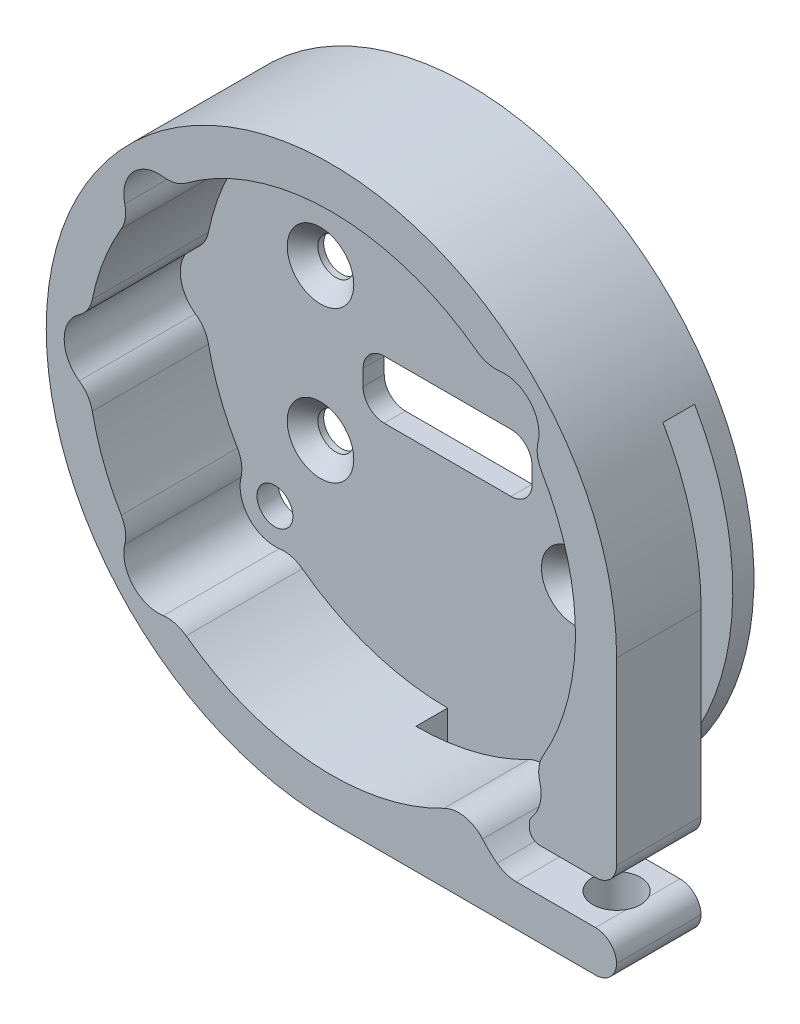
SolidWorks part; units mm, degrees
material "Сплав 2024"
ref_plane "Спереди" through (0, 0, 0) normal (0, 0, 1) x (1, 0, 0)
ref_plane "Сверху" through (0, 0, 0) normal (0, 1, 0) x (1, 0, 0)
ref_plane "Справа" through (0, 0, 0) normal (1, 0, 0) x (0, 0, -1)
sketch "Эскиз1" plane through (0, 0, 0) normal (0, 0, 1) x (1, 0, 0)
  circle A0 centre (0, 0) radius 23.1
  circle A1 centre (0, 0) radius 27
  dimension "D1" = 54
  dimension "D2" = 46.2
extrude "Бобышка-Вытянуть1" add sketch "Эскиз1" along normal blind 11
sketch "Эскиз2" plane through (0, 0, 0) normal (0, 0, -1) x (-1, 0, 0)
  circle A0 centre (0, 0) radius 27 construction
  circle A1 centre (0, 0) radius 27
extrude "Бобышка-Вытянуть2" add sketch "Эскиз2" along normal blind 2
sketch "Эскиз3" plane through (0, 0, 11) normal (0, 0, 1) x (1, 0, 0)
  line L0 (0, -27) -> (27, -27)
  line L1 (27, -27) -> (27, 0)
  circle A0 centre (0, 0) radius 27 construction
  arc A1 (27, 0) -> (0, -27) centre (0, 0) cw
extrude "Бобышка-Вытянуть3" add sketch "Эскиз3" against normal blind 8
sketch "Эскиз4" plane through (0, 0, 11) normal (0, 0, 1) x (1, 0, 0)
  line L0 (0, -23.1) -> (27, -23.1)
  line L1 (27, -27) -> (27, 0) construction
  line L2 (27, -23.1) -> (27, -19)
  line L3 (27, -19) -> (13.1381, -19)
  circle A0 centre (0, 0) radius 23.1 construction
  circle A1 centre (0, 0) radius 23.1 construction
  arc A2 (0, -23.1) -> (13.1381, -19) centre (0, 0) ccw
  dimension "D1" = 4.1
extrude "Вырез-Вытянуть1" cut sketch "Эскиз4" against normal blind 8
sketch "Эскиз5" plane through (0, -27, 0) normal (0, -1, 0) x (1, 0, 0)
  line L0 (23, 11) -> (23, 3) construction
  line L1 (0, 11) -> (27, 11) construction
  line L2 (0, 3) -> (27, 3) construction
  line L3 (27, 3) -> (27, 11) construction
  point P8 (23, 7)
  dimension "D1" = 4
hole_wizard "Отверстие с зазором M41" positions "Эскиз7" profile "Эскиз6" hole size "M4" standard "Ansi Metric" end condition up to next
sketch "Эскиз7" plane through (0, -27, 0) normal (0, -1, 0) x (-1, 0, 0)
  point P0 (-23, -7)
sketch "Эскиз6" plane through (23, -27, 7) normal (1, 0, 0) x (0, 0, -1)
  line L0 (0, 0) -> (0, 3.9)
  line L1 (0, 3.9) -> (2.25, 3.9)
  line L2 (2.25, 3.9) -> (2.25, 0)
  line L5 (2.25, 0) -> (0, 0)
  line L11 (0, -6.35) -> (0, 107.95) construction
  dimension "Диаметр сквозного отверстия" = 4.5
  dimension "Глубина сквозного отверстия" = 3.9
hole_wizard "Отверстие обработанное метчиком M4x0.71" positions "Эскиз9" profile "Эскиз8" tap size "M4x0.7" standard "Ansi Metric"
sketch "Эскиз9" plane through (0, -19, 0) normal (0, -1, 0) x (-1, 0, 0)
  point P0 (-23, -7)
cosmetic thread "Отверстие резьбы1" parameters "D1"=7, "D2"=4
sketch "Эскиз8" plane through (23, -19, 7) normal (1, 0, 0) x (0, 0, -1)
  line L0 (0, 0) -> (0, 11.4914)
  line L1 (0, 11.4914) -> (1.65, 10.5)
  line L2 (1.65, 10.5) -> (1.65, 0)
  line L5 (1.65, 0) -> (0, 0)
  line L10 (0, 11.4914) -> (-1.65, 10.5) construction
  line L11 (0, -6.35) -> (0, 107.95) construction
  dimension "Диаметр сверла" = 3.3
  dimension "Глубина сверла" = 10.5
  dimension "Угол заточки сверла" = 118
sketch "Эскиз10" plane through (0, 0, 3) normal (0, 0, 1) x (1, 0, 0)
  line L0 (0, 0) -> (0, -29.8506) construction
  line L1 (0, 0) -> (26.6177, 15.3678) construction
  line L2 (20.0052, 11.55) -> (23.3827, 13.5)
  line L3 (0, -23.1) -> (0, -27)
  circle A0 centre (0, 0) radius 23.1 construction
  arc A1 (27, 0) -> (0, -27) centre (0, 0) ccw construction
  arc A2 (0, -23.1) -> (20.0052, 11.55) centre (0, 0) ccw
  arc A3 (0, -27) -> (23.3827, 13.5) centre (0, 0) ccw
  point P3 (0, -23.1)
  point P5 (0, -27)
  point P8 (20.0052, 11.55)
  point P10 (23.3827, 13.5)
  dimension "D1" = 120
extrude "Вырез-Вытянуть2" cut sketch "Эскиз10" against normal blind 3
fillet "Скругление1" radius 2 3 edges at (27, -23.1, 7) (27, -27, 7) (27, -19, 7)
sketch "Эскиз11" plane through (0, 0, 0) normal (0, 0, 1) x (1, 0, 0)
  line L1 (-8, 2.75) -> (8, 2.75)
  line L2 (-8, 2.75) -> (-8, -2.75)
  line L3 (-8, -2.75) -> (8, -2.75)
  line L4 (8, 2.75) -> (8, -2.75)
  line L5 (-8, 2.75) -> (8, -2.75) construction
  line L6 (-8, -2.75) -> (8, 2.75) construction
  point P0 (0, 0)
  dimension "D2" = 5.5
  dimension "D1" = 16
extrude "Вырез-Вытянуть3" cut sketch "Эскиз11" against normal through all
sketch "Эскиз12" plane through (0, 0, 11) normal (0, 0, 1) x (1, 0, 0)
  circle A0 centre (0, 22) radius 3
  circle A1 centre (-22, 0) radius 3
  point P7 (0, 0)
  dimension "D1" = 6
  dimension "D2" = 22
  dimension "D3" = 2
extrude "Вырез-Вытянуть4" [suppressed] cut sketch "Эскиз12" against normal up to surface (11 mm away)
fillet "Скругление2" [suppressed] radius 3
sketch "Эскиз13" plane through (0, 0, -2) normal (0, 0, -1) x (-1, 0, 0)
  point P0 (0, 0)
sketch "Эскиз14" plane through (0, 0, 0) normal (0, 0, 1) x (1, 0, 0)
  line L0 (-36.5668, 0) -> (36.5668, 0) construction
  line L1 (22.6491, 20.3933) -> (-22.6491, -20.3933) construction
  line L2 (-23.4959, 21.1558) -> (23.4959, -21.1558) construction
  circle A0 centre (0, 0) radius 20.5 construction
  dimension "D1" = 41
  dimension "D2" = 42
  dimension "D3" = 96
sketch "Эскиз15" plane through (0, 0, 0) normal (0, 0, 1) x (1, 0, 0)
  line L0 (-23.4959, 21.1558) -> (23.4959, -21.1558) construction
  line L6 (-36.5668, 0) -> (36.5668, 0) construction
  line L7 (22.6491, 20.3933) -> (-22.6491, -20.3933) construction
  circle A0 centre (-16.3492, 14.7209) radius 1.75 construction
  circle A1 centre (-16.3492, 14.7209) radius 3.3
  circle A2 centre (16.3492, 14.7209) radius 3.3
  circle A3 centre (16.3492, 14.7209) radius 1.75 construction
  circle A4 centre (16.3492, -14.7209) radius 3.5
  circle A5 centre (16.3492, -14.7209) radius 1.75 construction
  circle A6 centre (-16.3492, -14.7209) radius 3.3
  circle A7 centre (-16.3492, -14.7209) radius 1.75 construction
  circle A8 centre (0, 0) radius 22 construction
  circle A10 centre (-22, 0) radius 3.3
  point P18 (0, 0)
  dimension "D1" = 3.5
  dimension "D3" = 6.6
  dimension "D4" = 6.6
  dimension "D5" = 6.6
  dimension "D6" = 7
  dimension "D2" = 44
  dimension "D7" = 6.6
extrude "Вырез-Вытянуть5" cut sketch "Эскиз15" along normal through all
fillet "Скругление3" radius 3 9 edges at (14.875, 17.6733, 5.5) (19.1313, 12.9461, 5.5) (-14.875, -17.6733, 5.5) (-14.875, 17.6733, 5.5) (-19.1313, -12.9461, 5.5) (-19.1313, 12.9461, 5.5) (19.2522, -12.7657, 7) (-22.88, -3.1805, 5.5) (-22.88, 3.1805, 5.5)
sketch "Эскиз16" plane through (0, 0, 11) normal (0, 0, 1) x (1, 0, 0)
  line L1 (12.6438, -16.5683) -> (18.7322, -16.5683)
  line L2 (12.6438, -16.5683) -> (12.6438, -19.7064)
  line L3 (12.6438, -19.7064) -> (18.7322, -19.7064)
  line L4 (18.7322, -16.5683) -> (18.7322, -19.7064)
extrude "Вырез-Вытянуть6" cut sketch "Эскиз16" against normal up to surface (11 mm away) up to face at (-5.4949, 1.7298, 0)
fillet "Скругление6" [suppressed] radius 1
hole_wizard "Отверстие с зазором M31" positions "Эскиз18" profile "Эскиз17" hole size "M3" standard "Ansi Metric"
sketch "Эскиз18" plane through (0, 0, 0) normal (0, 0, 1) x (1, 0, 0)
  point P0 (-16.3492, 14.7209)
  point P3 (16.3492, 14.7209)
  point P6 (16.3492, -14.7209)
  point P9 (-16.3492, -14.7209)
sketch "Эскиз17" plane through (-16.3492, 14.7209, 0) normal (1, 0, 0) x (0, -1, 0)
  line L0 (0, 0) -> (0, 19.0215)
  line L1 (0, 19.0215) -> (1.7, 18)
  line L2 (1.7, 18) -> (1.7, 0)
  line L5 (1.7, 0) -> (0, 0)
  line L10 (0, 19.0215) -> (-1.7, 18) construction
  line L11 (0, -6.35) -> (0, 107.95) construction
  dimension "Диаметр отверстия" = 3.4
  dimension "Глубина отверстия" = 18
  dimension "Угол заточки сверла" = 118
ref_axis "Ось1" through (0, 0, 11) along (0, 0, -1)
hole_wizard "Зенковка для  винта с плоской головкой M31" positions "Эскиз20" profile "Эскиз19" countersink size "M3" standard "Ansi Metric" end condition through all
sketch "Эскиз20" plane through (0, 0, 0) normal (0, 0, 1) x (1, 0, 0)
  line L0 (-18.5, 11) -> (18.5, -11) construction
  line L1 (18.5, 11) -> (-18.5, -11) construction
  circle A0 centre (0, 0) radius 14 construction
  point P0 (-12.0335, 7.1551)
  point P6 (-12.0335, -7.1551)
  point P10 (12.0335, -7.1551)
  point P12 (12.0335, 7.1551)
sketch "Эскиз19" plane through (-12.0335, 7.1551, 0) normal (1, 0, 0) x (0, -1, 0)
  line L0 (0, 0) -> (0, 2)
  line L1 (0, 2) -> (1.7, 2)
  line L2 (1.7, 2) -> (1.7, 1.45)
  line L3 (1.7, 1.45) -> (3.15, 0)
  line L5 (3.15, 0) -> (0, 0)
  line L6 (-1.7, 1.45) -> (-3.15, 0) construction
  line L11 (0, -6.35) -> (0, 107.95) construction
  dimension "Диаметр сквозного отверстия" = 3.4
  dimension "Глубина сквозного отверстия" = 2
  dimension "Диаметр передней зенковки" = 6.3
  dimension "Угол передней зенковки" = 90
fillet "Скругление7" radius 2 4 edges at (8, 2.75, -1) (8, -2.75, -1) (-8, -2.75, -1) (-8, 2.75, -1)
sketch "Эскиз21" plane through (0, 0, 11) normal (0, 0, 1) x (1, 0, 0)
  line L0 (0, -23.1) -> (25, -23.1) construction
  line L1 (16.5961, -23.1) -> (0, -23.1)
  arc A0 (0, -23.1) -> (12.9587, -19.1228) centre (0, 0) ccw
  arc A1 (-13.7546, -18.5586) -> (0, -23.1) centre (0, 0) ccw construction
  arc A2 (12.9587, -19.1228) -> (16.5961, -23.1) centre (21.2647, -15.1782) ccw
  arc A3 (-13.7546, -18.5586) -> (0, -23.1) centre (0, 0) ccw construction
extrude "Бобышка-Вытянуть4" add sketch "Эскиз21" against normal up to surface (8 mm away) up to face at (15.5586, -25.05, 3)
fillet "Скругление8" radius 3 2 edges at (16.5961, -23.1, 7) (12.9587, -19.1228, 7)
fillet "Скругление9" radius 1 2 edges at (18.7322, -17.2843, 7) (18.7322, -19, 7)
equation "\"D4@Эскиз15\"=\"D3@Эскиз15\""
equation "\"D5@Эскиз15\"=\"D3@Эскиз15\""
equation "\"D7@Эскиз15\"=\"D3@Эскиз15\""
